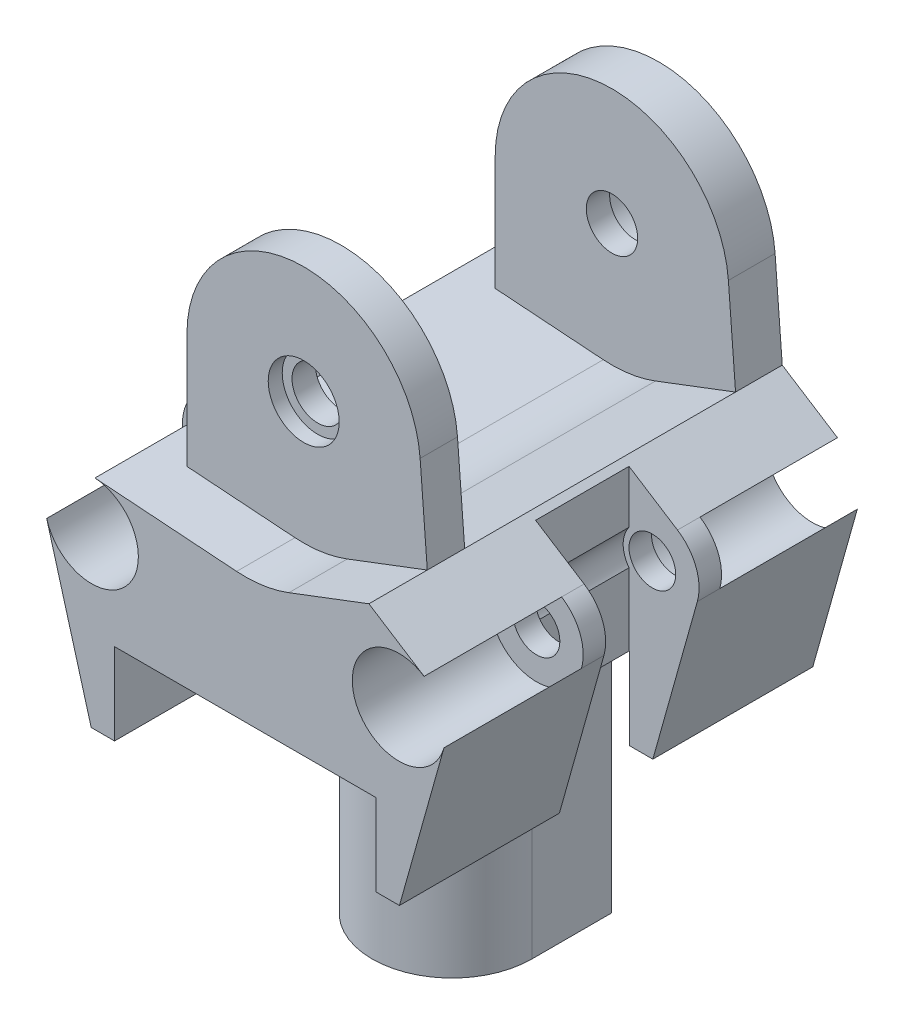
SolidWorks part; units mm, degrees
ref_plane "Front Plane" through (0, 0, 0) normal (0, 0, 1) x (1, 0, 0)
ref_plane "Top Plane" through (0, 0, 0) normal (0, 1, 0) x (1, 0, 0)
ref_plane "Right Plane" through (0, 0, 0) normal (1, 0, 0) x (0, 0, -1)
sketch "Sketch2" plane through (0, 0, 0) normal (0, 0, 1) x (1, 0, 0)
  line L0 (-15.8283, 34.9982) -> (-17.78, 9.5982)
  line L1 (15.8283, 34.9982) -> (17.78, 9.5982)
  line L2 (-17.78, 9.5982) -> (-17.78, 0)
  line L3 (-17.78, 0) -> (17.78, 0)
  line L4 (17.78, 0) -> (17.78, 9.5982)
  arc A0 (15.8283, 34.9982) -> (-15.8283, 34.9982) centre (0, 33.782) ccw
  circle A1 centre (0, 33.782) radius 15.875 construction
  circle A2 centre (0, 33.782) radius 3.4925
  point P14 (0, 0)
  dimension "D1" = 31.75
  dimension "D3" = 6.985
  dimension "D2" = 33.782
  dimension "D4" = 35.56
  dimension "D5" = 25.4
extrude "Boss-Extrude1" add sketch "Sketch2" along normal mid plane 56.1975
sketch "Sketch4" plane through (0, 0, -28.0987) normal (0, 0, -1) x (-1, 0, 0)
  line L0 (17.78, 0) -> (17.78, -11.1125)
  line L1 (17.78, -11.1125) -> (20.955, -11.1125)
  line L2 (20.955, -11.1125) -> (27.0068, 10.4782)
  line L3 (24.3084, 17.5449) -> (16.8013, 22.3355)
  line L6 (16.8013, 22.3355) -> (17.78, 9.5982)
  line L7 (17.78, 9.5982) -> (17.78, 0)
  line L8 (0, 0) -> (0, 49.657) construction
  line L9 (3.4925, 33.782) -> (-3.4925, 33.782) construction
  line L10 (-24.3084, 17.5449) -> (-16.8013, 22.3355)
  line L11 (-16.8013, 22.3355) -> (-17.78, 9.5982)
  line L12 (-17.78, 9.5982) -> (-17.78, 0)
  line L13 (-17.78, 0) -> (-17.78, -11.1125)
  line L14 (-17.78, -11.1125) -> (-20.955, -11.1125)
  line L15 (-20.955, -11.1125) -> (-27.0068, 10.4782)
  line L16 (15.8283, 34.9982) -> (17.78, 9.5982) construction
  line L17 (17.78, 9.5982) -> (17.78, 0) construction
  arc A0 (27.0068, 10.4782) -> (24.3084, 17.5449) centre (20.8924, 12.192) ccw
  circle A1 centre (20.8924, 12.192) radius 3.175
  circle A4 centre (-20.8924, 12.192) radius 3.175
  arc A5 (-27.0068, 10.4782) -> (-24.3084, 17.5449) centre (-20.8924, 12.192) cw
  arc A6 (15.8283, 34.9982) -> (-15.8283, 34.9982) centre (0, 33.782) ccw construction
  circle A7 centre (0, 33.782) radius 3.4925 construction
  point P45 (0, 33.782)
  dimension "D1" = 6.35
  dimension "D2" = 6.35
  dimension "D3" = 3.175
  dimension "D4" = 11.1125
  dimension "D5" = 3.302
  dimension "D6" = 21.59
  dimension "D7" = 12.7
extrude "Boss-Extrude3" add sketch "Sketch4" against normal up to surface (56.1975 mm away) up to face at (0, 17.3086, 28.0987)
ref_plane "Plane1.1" through (0, 0, -21.7487) normal (0, 0, -1) x (-1, 0, 0)
sketch "Sketch5" plane through (0, 0, -21.7487) normal (0, 0, 1) x (1, 0, 0)
  line L0 (-20.4416, 18.526) -> (-1.1834, 17.1553)
  line L3 (16.8013, 22.3355) -> (15.8283, 34.9982) construction
  line L4 (-16.8013, 22.3355) -> (-15.8283, 34.9982)
  line L6 (-24.3084, 17.5449) -> (-16.8013, 22.3355)
  line L7 (0, 33.782) -> (15.875, 33.782) construction
  line L8 (15.8283, 34.9982) -> (15.8283, 33.782) construction
  line L9 (-24.3084, 17.5449) -> (-16.8013, 22.3355) construction
  line L11 (15.8283, 34.9982) -> (16.8013, 22.3355)
  line L13 (5.9219, 18.2007) -> (16.8013, 22.3355)
  arc A0 (-24.3084, 17.5449) -> (-20.4416, 18.526) centre (-20.8924, 12.192) cw
  arc A2 (-1.1834, 17.1553) -> (5.9219, 18.2007) centre (0, 33.782) ccw
  arc A4 (15.8283, 34.9982) -> (-15.8283, 34.9982) centre (0, 33.782) ccw
  arc A6 (15.875, 33.782) -> (0, 17.907) centre (0, 33.782) cw construction
  circle A7 centre (0, 33.782) radius 3.4925 construction
  arc A8 (15.8283, 34.9982) -> (-15.8283, 34.9982) centre (0, 33.782) ccw construction
  arc A9 (-24.3084, 17.5449) -> (-27.0068, 10.4782) centre (-20.8924, 12.192) ccw construction
  dimension "D2" = 0.7937
extrude "Cut-Extrude1" cut sketch "Sketch5" along normal blind 36.83
ref_plane "Plane2.1" through (0, 0, 20.1612) normal (0, 0, -1) x (-1, 0, 0)
extrude "Cut-Extrude2" cut sketch "Sketch5<4>" along normal up to surface (49.8475 mm away) from surface up to face at (0, 10.1296, 28.0987) starting at plane "Plane2.1"
sketch "Sketch5<4>" plane through (0, 0, -21.7487) normal (0, 0, 1) x (1, 0, 0) same geometry as "Sketch5"
sketch "Sketch7" plane through (0, 0, 20.1612) normal (0, 0, 1) x (1, 0, 0)
  line L1 (-15.8283, 34.9982) -> (-16.8013, 22.3355)
  line L6 (-20.4416, 18.526) -> (-1.1834, 17.1553) construction
  line L7 (-15.875, 33.782) -> (-15.875, 18.201)
  line L9 (-15.875, 18.201) -> (-20.4416, 18.526)
  line L10 (-16.8013, 22.3355) -> (-24.3084, 17.5449)
  circle A2 centre (0, 33.782) radius 3.4925 construction
  arc A3 (-20.4416, 18.526) -> (-24.3084, 17.5449) centre (-20.8924, 12.192) ccw
  circle A5 centre (0, 33.782) radius 15.875 construction
  arc A6 (-15.8283, 34.9982) -> (-15.875, 33.782) centre (0, 33.782) ccw
  arc A7 (15.8283, 34.9982) -> (-15.8283, 34.9982) centre (0, 33.782) ccw construction
  arc A8 (-20.4416, 18.526) -> (-27.0068, 10.4782) centre (-20.8924, 12.192) ccw construction
extrude "Cut-Extrude3" cut sketch "Sketch7" against normal through all
ref_plane "Plane1" through (0, 0, -24.9237) normal (0, 0, 1) x (1, 0, 0)
sketch "Sketch8" plane through (0, 0, -24.9237) normal (0, 0, 1) x (1, 0, 0)
  circle A0 centre (0, 33.782) radius 4.826
  circle A3 centre (0, 33.782) radius 3.4925 construction
  dimension "D1" = 9.652
extrude "Cut-Extrude12" cut sketch "Sketch8" against normal up to surface (3.175 mm away) up to face at (3.4925, 33.782, -28.0987)
ref_plane "Plane2" through (0, 0, 18.2562) normal (0, 0, -1) x (-1, 0, 0)
extrude "Cut-Extrude13" cut sketch "Sketch8<3>" along normal up to surface (45.085 mm away) from surface up to face at (-3.4925, 33.782, 20.1612) starting at plane "Plane2"
sketch "Sketch8<3>" plane through (0, 0, -24.9237) normal (0, 0, 1) x (1, 0, 0) same geometry as "Sketch8"
sketch "Sketch9" plane through (0, 0, 0) normal (0, 1, 0) x (1, 0, 0)
  line L0 (15.8283, 28.0987) -> (-15.875, 28.0987) construction
  line L5 (-20.4416, -28.0988) -> (-1.1834, -28.0988) construction
  line L6 (-28.8299, -6.35) -> (-17.7174, -6.35)
  line L7 (-28.8299, -6.35) -> (-28.8299, 6.35)
  line L8 (-28.8299, 6.35) -> (-17.7174, 6.35)
  line L9 (-17.7174, -6.35) -> (-17.7174, 6.35)
  line L10 (-28.8299, 0) -> (0, 0) construction
  line L11 (27.2424, -28.0987) -> (27.2424, 28.0988) construction
  line L15 (0, -28.0988) -> (0, 28.0987) construction
  line L18 (17.7174, -6.35) -> (17.7174, 6.35)
  line L19 (28.8299, 6.35) -> (17.7174, 6.35)
  line L20 (28.8299, -6.35) -> (28.8299, 6.35)
  line L21 (28.8299, -6.35) -> (17.7174, -6.35)
  dimension "D1" = 12.7
  dimension "D2" = 11.1125
  dimension "D3" = 1.5875
extrude "Cut-Extrude5_MuscleExtrusions" cut sketch "Sketch9" against normal through all and the other way through all
sketch "Sketch10" plane through (0, 0, 0) normal (0, 0, 1) x (1, 0, 0)
  circle A0 centre (20.8924, 12.192) radius 3.9688
  circle A1 centre (-20.8924, 12.192) radius 3.9688
  circle A2 centre (-20.8924, 12.192) radius 3.175 construction
  circle A3 centre (20.8924, 12.192) radius 3.175 construction
  dimension "D1" = 7.9375
extrude "Cut-Extrude6_PinSpace" cut sketch "Sketch10" along direction (0, 0, 1) on the side of the normal up to surface (6.35 mm away) from surface up to face at (20.6908, 5.8198, 6.35) starting at face at (19.9852, 5.8198, -6.35)
sketch "Sketch11" plane through (0, 0, 0) normal (0, 1, 0) x (-1, 0, 0)
  line L0 (10.8585, 0) -> (10.8585, -10.8585)
  line L1 (10.8585, 10.8585) -> (-10.8585, 10.8585) construction
  line L7 (10.8585, 0) -> (10.8585, -10.8585) construction
  line L8 (10.8585, -10.8585) -> (-10.8585, -10.8585) construction
  line L10 (-10.8585, 0) -> (-10.8585, -10.8585) construction
  line L11 (10.8585, 10.8585) -> (-10.8585, -10.8585) construction
  line L12 (10.8585, -10.8585) -> (-10.8585, 10.8585) construction
  line L14 (10.8585, -10.8585) -> (-10.8585, -10.8585)
  line L15 (-10.8585, -10.8585) -> (-10.8585, 0)
  line L16 (10.8585, 0) -> (-10.8585, 0) construction
  arc A1 (10.8585, 0) -> (-10.8585, 0) centre (0, 0) ccw
  point P0 (0, 0)
  point P8 (0, 10.8585)
  point P11 (0, -10.8585)
  dimension "D2" = 21.717
  dimension "D1" = 21.717
extrude "Boss-Extrude2_BottomAttachment" add sketch "Sketch11" against normal blind 36.5125
sketch "Sketch12" plane through (0, -36.5125, 0) normal (0, -1, 0) x (1, 0, 0)
  line L13 (7.6835, -7.6835) -> (7.6835, 0)
  line L14 (-7.6835, 0) -> (-7.6835, -7.6835)
  line L15 (-7.6835, -7.6835) -> (7.6835, -7.6835)
  line L16 (7.6835, -7.6835) -> (7.6835, 0)
  line L17 (-7.6835, 0) -> (-7.6835, -7.6835)
  line L18 (-7.6835, -7.6835) -> (7.6835, -7.6835)
  arc A3 (7.6835, 0) -> (-7.6835, 0) centre (0, 0) ccw
  arc A5 (7.6835, 0) -> (-7.6835, 0) centre (0, 0) ccw
  dimension "D1" = 3.175
extrude "Cut-Extrude7_D=0.5_BottomCutout6" cut sketch "Sketch12" against normal blind 38.1
sketch "Sketch13" plane through (0, 0, 0) normal (0, 0, 1) x (1, 0, 0)
  line L0 (-17.7174, 14.5732) -> (-17.4302, 18.3116)
  line L1 (-20.4416, 18.526) -> (-1.1834, 17.1553) construction
  line L2 (-17.4302, 18.3116) -> (-17.7174, 18.3321)
  line L3 (-17.7174, 18.3321) -> (-17.7174, 14.5732)
  line L4 (0, 33.3375) -> (0, 0) construction
  line L5 (16.8013, 22.3355) -> (15.8283, 34.9982) construction
  line L6 (-16.8013, 22.3355) -> (-15.8283, 34.9982) construction
  line L7 (16.8013, 22.3355) -> (15.8283, 34.9982) construction
  line L8 (-15.875, 18.201) -> (-1.1834, 17.1553) construction
  line L9 (-17.7174, 14.5732) -> (-17.7174, 18.3321) construction
  arc A0 (15.8283, 34.9982) -> (-15.875, 33.782) centre (0, 33.782) ccw construction
extrude "Cut-Extrude10" cut sketch "Sketch13" against normal up to surface and the other way up to surface up to face at (-19.5698, 5.6888, -6.35) other way up to face at (-19.5698, 5.6888, 6.35)
sketch "Sketch14" plane through (0, 0, 28.0987) normal (0, 0, 1) x (1, 0, 0)
  line L4 (0, 49.657) -> (0, -21.0469) construction
  arc A0 (-20.8924, 18.542) -> (-20.8924, 5.842) centre (-20.8924, 12.192) ccw
  arc A1 (-20.4416, 18.526) -> (-27.0068, 10.4782) centre (-20.8924, 12.192) ccw construction
  arc A4 (-20.8924, 5.842) -> (-20.8924, 18.542) centre (-20.8924, 12.192) ccw
  arc A6 (20.8924, 18.542) -> (20.8924, 5.842) centre (20.8924, 12.192) ccw
  arc A7 (15.8283, 34.9982) -> (-15.875, 33.782) centre (0, 33.782) ccw construction
  arc A10 (20.8924, 5.842) -> (20.8924, 18.542) centre (20.8924, 12.192) ccw
  circle A14 centre (20.8924, 12.192) radius 3.175 construction
extrude "Cut-Extrude11" cut sketch "Sketch14" against normal blind 18.6944
mirror "Mirror1" about plane through (0, 0, 0) normal (0, 0, 1) of "Cut-Extrude11"
